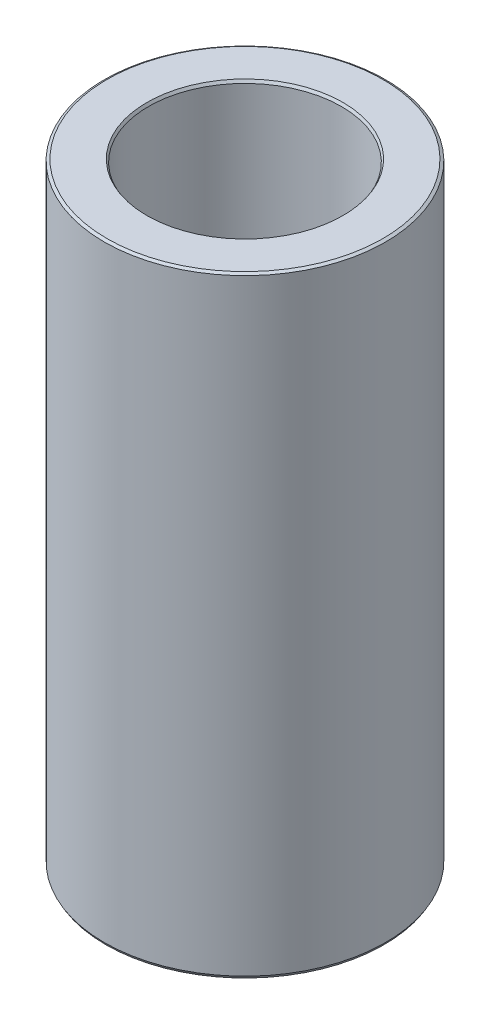
SolidWorks part; units mm, degrees
ref_plane "Front Plane" through (0, 0, 0) normal (0, 0, 1) x (1, 0, 0)
ref_plane "Top Plane" through (0, 0, 0) normal (0, 1, 0) x (1, 0, 0)
ref_plane "Right Plane" through (0, 0, 0) normal (1, 0, 0) x (0, 0, -1)
sketch "Sketch1" plane through (0, 0, 0) normal (0, 1, 0) x (1, 0, 0)
  circle A0 centre (0, 0) radius 25
  dimension "SLEEVE_OD" = 50
extrude "Boss-Extrude1" add sketch "Sketch1" along normal blind 108.6054
sketch "Sketch2" plane through (0, 0, 0) normal (0, 1, 0) x (1, 0, 0)
  circle A0 centre (0, 0) radius 17.1485
  dimension "BORE_D" = 34.2971
extrude "Cut-Extrude1" cut sketch "Sketch2" along normal through all
chamfer "Chamfer1" distance 0.28 angle 60 4 edges at (0, 108.6054, 17.1485) (0, 0, 17.1485) (0, 0, 25) (0, 108.6054, 25) first distance on face at (0, 108.6054, 17.1485) first distance on face at (0, 0, 17.1485) first distance on face at (0, 108.6054, 25)
